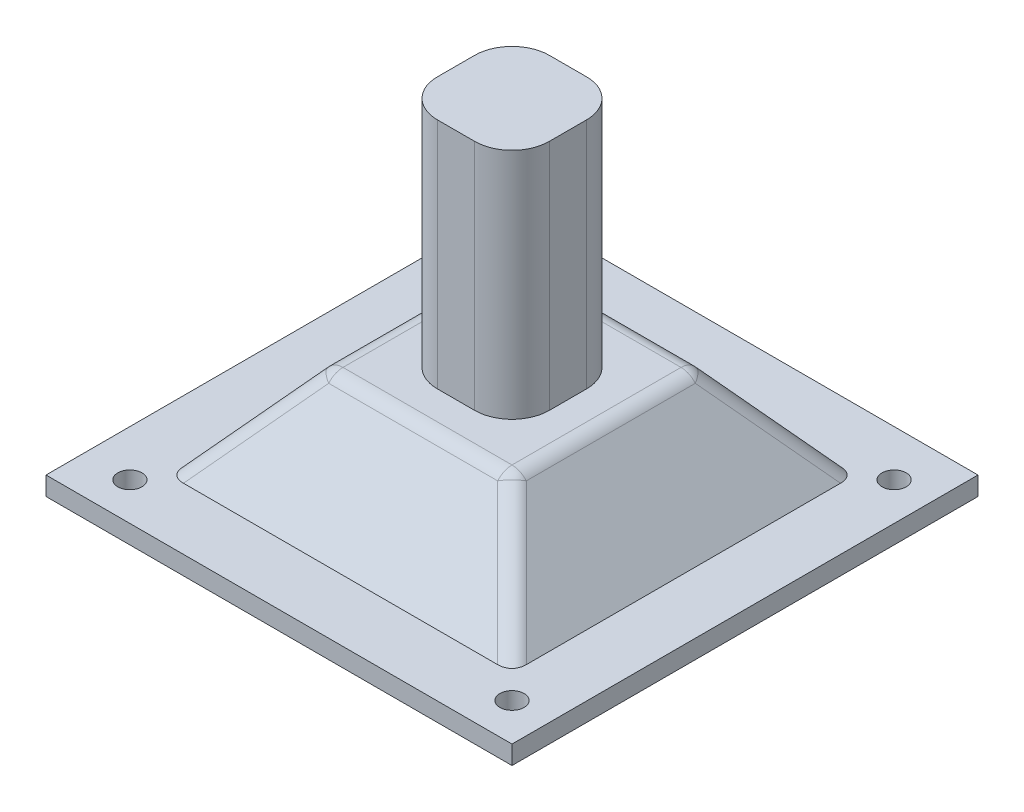
SolidWorks part; units mm, degrees
ref_plane "Front Plane" through (0, 0, 0) normal (0, 0, 1) x (1, 0, 0)
ref_plane "Top Plane" through (0, 0, 0) normal (0, 1, 0) x (1, 0, 0)
ref_plane "Right Plane" through (0, 0, 0) normal (1, 0, 0) x (0, 0, -1)
sketch "Sketch1" plane through (0, 0, 0) normal (0, 1, 0) x (1, 0, 0)
  line L1 (7.62, -7.62) -> (-7.62, -7.62)
  line L2 (7.62, -7.62) -> (7.62, 7.62)
  line L3 (7.62, 7.62) -> (-7.62, 7.62)
  line L4 (-7.62, -7.62) -> (-7.62, 7.62)
  line L5 (7.62, -7.62) -> (-7.62, 7.62) construction
  line L6 (7.62, 7.62) -> (-7.62, -7.62) construction
  point P0 (0, 0)
  dimension "D1" = 15.24
extrude "Boss-Extrude1" add sketch "Sketch1" along normal blind 31.75
fillet "Fillet1" radius 5.08 4 edges at (-7.62, 15.875, 7.62) (7.62, 15.875, 7.62) (7.62, 15.875, -7.62) (-7.62, 15.875, -7.62)
sketch "Sketch2" plane through (0, 0, 0) normal (0, -1, 0) x (1, 0, 0)
  line L1 (12.7, -12.7) -> (-12.7, -12.7)
  line L2 (12.7, -12.7) -> (12.7, 12.7)
  line L3 (12.7, 12.7) -> (-12.7, 12.7)
  line L4 (-12.7, -12.7) -> (-12.7, 12.7)
  line L5 (12.7, -12.7) -> (-12.7, 12.7) construction
  line L6 (12.7, 12.7) -> (-12.7, -12.7) construction
  point P0 (0, 0)
  dimension "D1" = 25.4
extrude "Boss-Extrude3" add sketch "Sketch2" along normal blind 12.7 draft 40 draft outward yes
sketch "Sketch5" plane through (0, -12.7, 0) normal (0, -1, 0) x (1, 0, 0)
  line L8 (-20.8166, 20.8166) -> (-20.8166, -20.8166)
  line L9 (-20.8166, -20.8166) -> (20.8166, -20.8166)
  line L10 (20.8166, -20.8166) -> (20.8166, 20.8166)
  line L11 (20.8166, 20.8166) -> (-20.8166, 20.8166)
  line L16 (-20.8166, 20.8166) -> (-20.8166, -20.8166)
  line L17 (-20.8166, -20.8166) -> (20.8166, -20.8166)
  line L18 (20.8166, -20.8166) -> (20.8166, 20.8166)
  line L19 (20.8166, 20.8166) -> (-20.8166, 20.8166)
  dimension "D1" = 2.54
extrude "Cut-Extrude1" cut sketch "Sketch5" against normal blind 10.16 draft 40
fillet "Fillet2" radius 2.54 8 edges at (-12.7, 0, 0) (0, 0, -12.7) (12.7, 0, 0) (0, 0, 12.7) (-18.0283, -6.35, -18.0283) (18.0283, -6.35, -18.0283) (18.0283, -6.35, 18.0283) (-18.0283, -6.35, 18.0283)
sketch "Sketch6" plane through (0, -12.7, 0) normal (0, -1, 0) x (1, 0, 0)
  line L5 (31.75, -31.75) -> (-31.75, -31.75)
  line L6 (31.75, -31.75) -> (31.75, 31.75)
  line L7 (31.75, 31.75) -> (-31.75, 31.75)
  line L8 (-31.75, -31.75) -> (-31.75, 31.75)
  line L9 (31.75, -31.75) -> (-31.75, 31.75) construction
  line L10 (31.75, 31.75) -> (-31.75, -31.75) construction
  point P0 (0, 0)
  dimension "D1" = 63.5
extrude "Boss-Extrude4" add sketch "Sketch6" along normal blind 2.54
sketch "Sketch7" plane through (0, -12.7, 0) normal (0, 1, 0) x (1, 0, 0)
  line L1 (-31.75, 31.75) -> (-25.4638, 25.4638) construction
  circle A0 centre (-25.4638, 25.4638) radius 1.651
  dimension "D2" = 3.302
  dimension "D1" = 8.89
extrude "Cut-Extrude2" cut sketch "Sketch7" against normal through all
pattern_linear "LPattern1" count 2 spacing 52.07 along (1, 0, 0) count 2 spacing 52.07 along (0, 0, 1) of "Cut-Extrude2"
